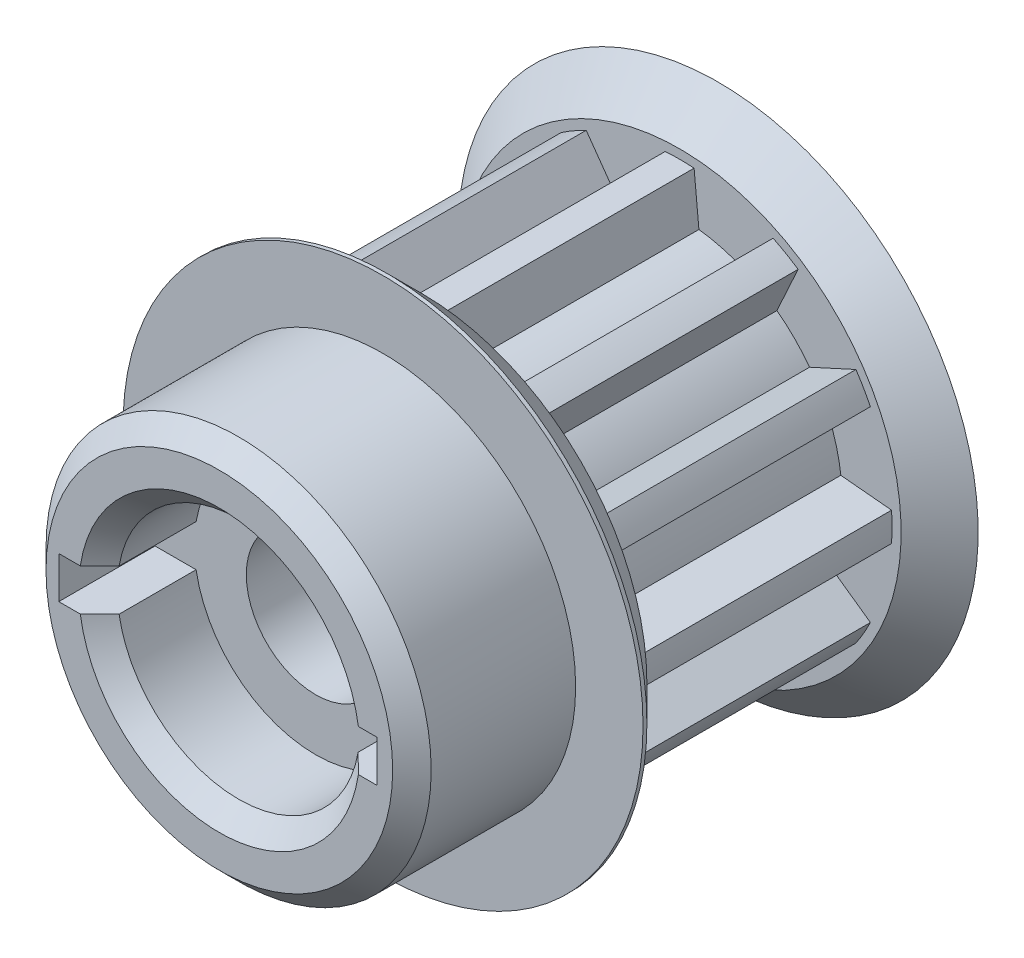
SolidWorks part; units mm, degrees
material "ABS"
ref_plane "Alzado" through (0, 0, 0) normal (0, 0, 1) x (1, 0, 0)
ref_plane "Planta" through (0, 0, 0) normal (0, 1, 0) x (1, 0, 0)
ref_plane "Vista lateral" through (0, 0, 0) normal (1, 0, 0) x (0, 0, -1)
sketch "Croquis1" plane through (0, 0, 0) normal (0, 0, 1) x (1, 0, 0)
  line L0 (0, 0) -> (0, 4.6049) construction
  line L1 (0.375, 5.5012) -> (0.5, 4.1842)
  line L2 (-0.375, 5.5012) -> (-0.5, 4.1842)
  line L3 (2.4259, 4.9517) -> (1.6591, 3.8737)
  line L4 (3.0754, 4.5767) -> (2.5251, 3.3737)
  line L5 (4.5767, 3.0754) -> (3.3737, 2.5251)
  line L6 (4.9517, 2.4259) -> (3.8737, 1.6591)
  line L7 (5.5012, 0.375) -> (4.1842, 0.5)
  line L8 (5.5012, -0.375) -> (4.1842, -0.5)
  line L9 (4.9517, -2.4259) -> (3.8737, -1.6591)
  line L10 (4.5767, -3.0754) -> (3.3737, -2.5251)
  line L11 (3.0754, -4.5767) -> (2.5251, -3.3737)
  line L12 (2.4259, -4.9517) -> (1.6591, -3.8737)
  line L13 (0.375, -5.5012) -> (0.5, -4.1842)
  line L14 (-0.375, -5.5012) -> (-0.5, -4.1842)
  line L15 (-2.4259, -4.9517) -> (-1.6591, -3.8737)
  line L16 (-3.0754, -4.5767) -> (-2.5251, -3.3737)
  line L17 (-4.5767, -3.0754) -> (-3.3737, -2.5251)
  line L18 (-4.9517, -2.4259) -> (-3.8737, -1.6591)
  line L19 (-5.5012, -0.375) -> (-4.1842, -0.5)
  line L20 (-5.5012, 0.375) -> (-4.1842, 0.5)
  line L21 (-4.9517, 2.4259) -> (-3.8737, 1.6591)
  line L22 (-4.5767, 3.0754) -> (-3.3737, 2.5251)
  line L23 (-3.0754, 4.5767) -> (-2.5251, 3.3737)
  line L24 (-2.4259, 4.9517) -> (-1.6591, 3.8737)
  circle A0 centre (0, 0) radius 1.8
  arc A1 (1.6591, 3.8737) -> (0.5, 4.1842) centre (0, 0) ccw
  arc A2 (3.0754, 4.5767) -> (2.4259, 4.9517) centre (0, 0) ccw
  arc A3 (4.9517, 2.4259) -> (4.5767, 3.0754) centre (0, 0) ccw
  arc A4 (5.5012, -0.375) -> (5.5012, 0.375) centre (0, 0) ccw
  arc A5 (4.5767, -3.0754) -> (4.9517, -2.4259) centre (0, 0) ccw
  arc A6 (2.4259, -4.9517) -> (3.0754, -4.5767) centre (0, 0) ccw
  arc A7 (-0.375, -5.5012) -> (0.375, -5.5012) centre (0, 0) ccw
  arc A8 (-3.0754, -4.5767) -> (-2.4259, -4.9517) centre (0, 0) ccw
  arc A9 (-4.9517, -2.4259) -> (-4.5767, -3.0754) centre (0, 0) ccw
  arc A10 (-5.5012, 0.375) -> (-5.5012, -0.375) centre (0, 0) ccw
  arc A11 (-4.5767, 3.0754) -> (-4.9517, 2.4259) centre (0, 0) ccw
  arc A12 (-2.4259, 4.9517) -> (-3.0754, 4.5767) centre (0, 0) ccw
  arc A13 (0.375, 5.5012) -> (-0.375, 5.5012) centre (0, 0) ccw
  arc A14 (3.3737, 2.5251) -> (2.5251, 3.3737) centre (0, 0) ccw
  arc A15 (4.1842, 0.5) -> (3.8737, 1.6591) centre (0, 0) ccw
  arc A16 (3.8737, -1.6591) -> (4.1842, -0.5) centre (0, 0) ccw
  arc A17 (2.5251, -3.3737) -> (3.3737, -2.5251) centre (0, 0) ccw
  arc A18 (0.5, -4.1842) -> (1.6591, -3.8737) centre (0, 0) ccw
  arc A19 (-1.6591, -3.8737) -> (-0.5, -4.1842) centre (0, 0) ccw
  arc A20 (-3.3737, -2.5251) -> (-2.5251, -3.3737) centre (0, 0) ccw
  arc A21 (-4.1842, -0.5) -> (-3.8737, -1.6591) centre (0, 0) ccw
  arc A22 (-3.8737, 1.6591) -> (-4.1842, 0.5) centre (0, 0) ccw
  arc A23 (-2.5251, 3.3737) -> (-3.3737, 2.5251) centre (0, 0) ccw
  arc A24 (-0.5, 4.1842) -> (-1.6591, 3.8737) centre (0, 0) ccw
  dimension "D1" = 1
  dimension "D2" = 3.6
  dimension "D4" = 1.3
  dimension "D3" = 0.75
  dimension "D6" = 1.2
  dimension "D5" = 12
extrude "Saliente-Extruir1" add sketch "Croquis1" along normal blind 6.7
sketch "Croquis2" plane through (0, 0, 6.7) normal (0, 0, 1) x (1, 0, 0)
  circle A0 centre (0, 0) radius 3.15
  circle A1 centre (0, 0) radius 5
  dimension "D1" = 10
  dimension "D2" = 6.3
extrude "Saliente-Extruir2" add sketch "Croquis2" along normal blind 5.25
chamfer "Chaflán1" distance 0.5 angle 45 1 edges at (5, 0, 11.95)
sketch "Croquis3" plane through (0, 0, 0) normal (0, 0, -1) x (-1, 0, 0)
  circle A0 centre (0, 0) radius 1.8
  circle A1 centre (0, 0) radius 6.75
  circle A2 centre (0, 0) radius 1.8 construction
  dimension "D1" = 13.5
extrude "Saliente-Extruir3" add sketch "Croquis3" along normal blind 1
chamfer "Chaflán2" distance 0.5 angle 45 1 edges at (3.15, 0, 11.95)
sketch "Croquis4" plane through (0, 0, 6.7) normal (0, 0, 1) x (1, 0, 0)
  circle A0 centre (0, 0) radius 1.8
  circle A1 centre (0, 0) radius 4.8926
  circle A2 centre (0, 0) radius 1.8 construction
extrude "Saliente-Extruir4" add sketch "Croquis4" along normal blind 2.75
chamfer "Chaflán3" distance 0.5 angle 45 12 edges at (4.0704, 1.0907, 6.7) (2.9798, 2.9798, 6.7) (1.0907, 4.0704, 6.7) (-1.0907, 4.0704, 6.7) (-2.9798, 2.9798, 6.7) (-4.0704, -1.0907, 6.7) (-4.0704, 1.0907, 6.7) (-2.9798, -2.9798, 6.7) (-1.0907, -4.0704, 6.7) (1.0907, -4.0704, 6.7) (2.9798, -2.9798, 6.7) (4.0704, -1.0907, 6.7)
chamfer "Chaflán4" distance 1 angle 45 1 edges at (-6.75, 0, 0)
sketch "Croquis6" plane through (0, 0, 6.7) normal (0, 0, 1) x (1, 0, 0)
  circle A0 centre (0, 0) radius 6.75
  circle A2 centre (0, 0) radius 1.8
  circle A4 centre (0, 0) radius 1.8 construction
  dimension "D1" = 13.5
extrude "Saliente-Extruir5" add sketch "Croquis6" along normal blind 1
chamfer "Chaflán5" distance 0.9 angle 45 1 edges at (6.75, 0, 6.7)
sketch "Croquis8" plane through (0, 0, -1) normal (0, 0, -1) x (-1, 0, 0)
  line L1 (-1.4602, -2.3077) -> (1.2684, -2.4184)
  line L2 (1.2684, -2.4184) -> (2.7286, -0.1108)
  line L3 (2.7286, -0.1108) -> (1.4602, 2.3077)
  line L4 (1.4602, 2.3077) -> (-1.2684, 2.4184)
  line L5 (-1.2684, 2.4184) -> (-2.7286, 0.1108)
  line L6 (-2.7286, 0.1108) -> (-1.4602, -2.3077)
  circle A0 centre (0, 0) radius 2.365 construction
  dimension "D1" = 4.73
extrude "Cortar-Extruir1" cut sketch "Croquis8" against normal blind 8
chamfer "Chaflán6" distance 1 angle 45 6 edges at (-0.0959, 2.3631, -1) (1.9985, 1.2646, -1) (2.0944, -1.0985, -1) (0.0959, -2.3631, -1) (-1.9985, -1.2646, -1) (-2.0944, 1.0985, -1)
chamfer "Chaflán7" distance 1 angle 45 1 edges at (-1.8, 0, 7)
sketch "Croquis9" plane through (0, 0, 11.95) normal (0, 0, 1) x (1, 0, 0)
  line L0 (5.7484, 0) -> (-6.3843, 0) construction
  line L1 (4.0984, -0.5408) -> (4.0984, 0.5408)
  line L2 (4.0984, 0.5408) -> (-4.1681, 0.5408)
  line L3 (-4.1681, 0.5408) -> (-4.1681, -0.5408)
  line L4 (-4.1681, -0.5408) -> (4.0984, -0.5408)
extrude "Cortar-Extruir2" cut sketch "Croquis9" against normal up to surface (2.5 mm away) up to face at (1.8, 0, 9.45)
